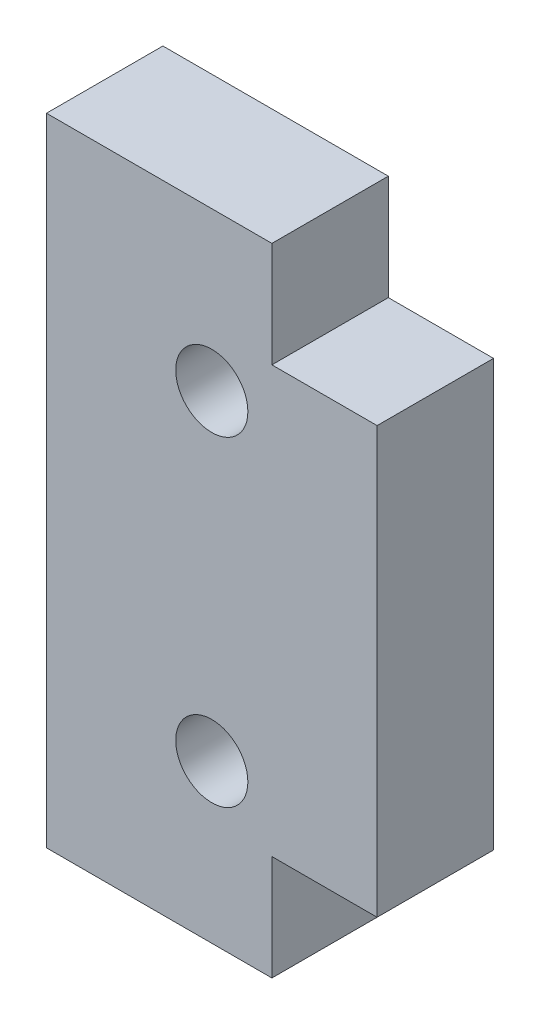
SolidWorks part; units mm, degrees
ref_plane "Front Plane" through (0, 0, 0) normal (0, 0, 1) x (1, 0, 0)
ref_plane "Top Plane" through (0, 0, 0) normal (0, 1, 0) x (1, 0, 0)
ref_plane "Right Plane" through (0, 0, 0) normal (1, 0, 0) x (0, 0, -1)
sketch "Sketch2" plane through (0, 0, 0) normal (0, 0, 1) x (1, 0, 0)
  line L0 (8.25, -152.4) -> (8.25, 152.4) construction
  line L1 (8.25, -39.1052) -> (-8.25, -39.1052)
  line L2 (8.25, -39.1052) -> (8.25, -7.3552)
  line L3 (8.25, -7.3552) -> (-8.25, -7.3552)
  line L4 (-8.25, -39.1052) -> (-8.25, -7.3552)
  line L5 (-8.25, -152.4) -> (-8.25, 152.4) construction
extrude "Boss-Extrude1" add sketch "Sketch2" along normal up to surface (5.81 mm away)
sketch "Sketch3" plane through (0, 0, 5.81) normal (0, 0, 1) x (1, 0, 0)
  line L0 (3.6, -31.2302) -> (3.6, -15.2302) construction
  line L1 (3.6, -34.8302) -> (-3.6, -34.8302)
  line L2 (3.6, -34.8302) -> (3.6, -11.6302)
  line L3 (3.6, -11.6302) -> (-3.6, -11.6302)
  line L4 (-3.6, -34.8302) -> (-3.6, -11.6302)
  line L5 (-4.4, -34.8302) -> (0, -34.8302) construction
  line L6 (0, -11.6302) -> (-4.4, -11.6302) construction
  circle A0 centre (0, -31.2302) radius 2.4 construction
  dimension "D1" = 3.6
extrude "Boss-Extrude2" [suppressed] add sketch "Sketch3" along normal up to surface (6 mm away)
sketch "Sketch4" [suppressed] plane through (0, 0, 11.81) normal (0, 0, 1) x (1, 0, 0)
  circle A4 centre (0, -31.2302) radius 2.8
  circle A5 centre (0, -15.2302) radius 2.8
extrude "Cut-Extrude1" [suppressed] cut sketch "Sketch4" against normal through all
sketch "Sketch5" plane through (0, 0, 5.81) normal (0, 0, 1) x (1, 0, 0)
  line L0 (3, -152.4) -> (3, 152.4) construction
  line L1 (8.25, -39.1052) -> (3, -39.1052)
  line L2 (8.25, -39.1052) -> (8.25, -33.8552)
  line L3 (8.25, -33.8552) -> (3, -33.8552)
  line L4 (3, -39.1052) -> (3, -33.8552)
  line L5 (8.25, -7.3552) -> (3, -7.3552)
  line L6 (8.25, -7.3552) -> (8.25, -12.6052)
  line L7 (8.25, -12.6052) -> (3, -12.6052)
  line L8 (3, -7.3552) -> (3, -12.6052)
extrude "Cut-Extrude2" cut sketch "Sketch5" against normal through all
sketch "Sketch6" plane through (0, 0, 5.81) normal (0, 0, 1) x (1, 0, 0)
  circle A0 centre (0, -15.2302) radius 2.4 construction
  circle A1 centre (0, -31.2302) radius 2.4 construction
  circle A2 centre (0, -15.2302) radius 2.4 construction
  circle A3 centre (0, -31.2302) radius 2.4 construction
  circle A4 centre (0, -31.2302) radius 1.8
  circle A5 centre (0, -15.2302) radius 1.8
  dimension "D1" = 0.6
extrude "Cut-Extrude3" cut sketch "Sketch6" against normal through all
